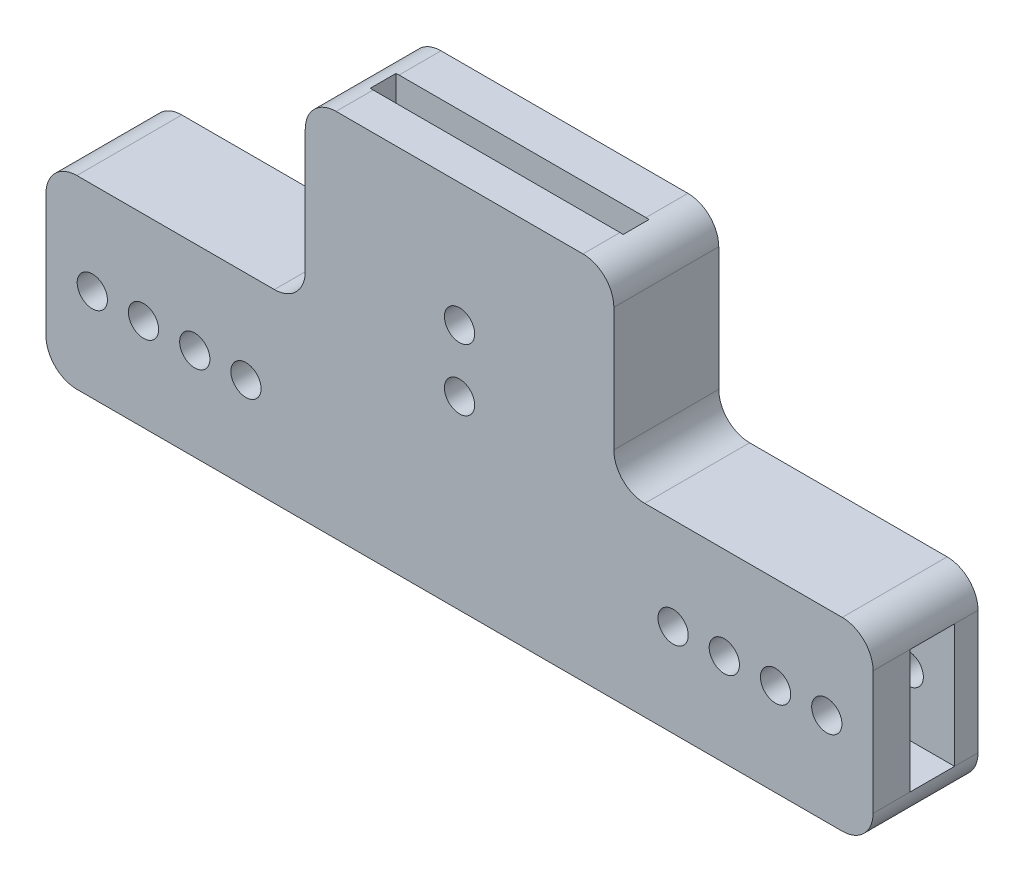
SolidWorks part; units mm, degrees
ref_plane "Front Plane" through (0, 0, 0) normal (0, 0, 1) x (1, 0, 0)
ref_plane "Top Plane" through (0, 0, 0) normal (0, 1, 0) x (1, 0, 0)
ref_plane "Right Plane" through (0, 0, 0) normal (1, 0, 0) x (0, 0, -1)
sketch "Sketch1" plane through (0, 0, 0) normal (0, 0, 1) x (1, 0, 0)
  line L1 (-25, 30) -> (25, 30)
  line L2 (-25, 30) -> (-25, -30)
  line L3 (-25, -30) -> (25, -30)
  line L4 (25, 30) -> (25, -30)
  line L5 (-25, 30) -> (25, -30) construction
  line L6 (-25, -30) -> (25, 30) construction
  point P0 (0, 0)
extrude "Boss-Extrude1" add sketch "Sketch1" along normal blind 12
sketch "Sketch2" plane through (0, 30, 0) normal (0, 1, 0) x (1, 0, 0)
  line L0 (0, 0) -> (0, -12) construction
  line L1 (-20.5, -6.8) -> (20.5, -6.8)
  line L2 (-20.5, -6.8) -> (-20.5, -11)
  line L3 (-20.5, -11) -> (20.5, -11)
  line L4 (20.5, -6.8) -> (20.5, -11)
  line L5 (-20.5, -6.8) -> (20.5, -11) construction
  line L6 (-20.5, -11) -> (20.5, -6.8) construction
  line L7 (25, 0) -> (-25, 0) construction
  line L8 (-25, -6) -> (25, -6) construction
  line L9 (-25, -12) -> (-25, 0) construction
  line L10 (25, -12) -> (25, 0) construction
  line L11 (25, -12) -> (-25, -12) construction
  point P0 (0, -8.9)
  dimension "D1" = 1
  dimension "D2" = 4.2
  dimension "D3" = 41
extrude "Cut-Extrude1" cut sketch "Sketch2" against normal through all
sketch "Sketch3" plane through (-25, 0, 0) normal (-1, 0, 0) x (0, 0, 1)
  line L0 (12, 30) -> (12, -30) construction
  line L1 (0, -30) -> (12, -30)
  line L2 (0, -30) -> (0, 0)
  line L3 (0, 0) -> (12, 0)
  line L4 (12, -30) -> (12, 0)
  line L5 (6, 0) -> (6, -30) construction
  line L6 (0, -15) -> (12, -15) construction
  point P1024 (6, -15)
  dimension "D1" = 30
extrude "Boss-Extrude2" add sketch "Sketch3" along normal blind 42
sketch "Sketch4" plane through (-67, 0, 0) normal (-1, 0, 0) x (0, 0, 1)
  line L0 (12, 0) -> (0, 0) construction
  line L1 (3.8, -5) -> (11, -5)
  line L2 (3.8, -5) -> (3.8, -25)
  line L3 (3.8, -25) -> (11, -25)
  line L4 (11, -5) -> (11, -25)
  line L5 (3.8, -5) -> (11, -25) construction
  line L6 (3.8, -25) -> (11, -5) construction
  line L7 (12, -30) -> (12, 0) construction
  line L9 (0, -30) -> (12, -30) construction
  line L10 (6, 0) -> (6, -30) construction
  point P0 (7.4, -15)
  dimension "D1" = 5
  dimension "D2" = 1
  dimension "D3" = 7.2
  dimension "D4" = 5
extrude "Cut-Extrude2" cut sketch "Sketch4" against normal blind 42.5
sketch "Sketch5" plane through (0, 0, 12) normal (0, 0, 1) x (1, 0, 0)
  line L0 (-67, -5) -> (-67, -25) construction
  circle A0 centre (-59.5, -14.9958) radius 2.45
  circle A1 centre (-51.2, -14.9958) radius 2.45
  circle A2 centre (-42.9, -14.9958) radius 2.45
  circle A3 centre (-34.6, -14.9958) radius 2.45
  dimension "D1" = 4
  dimension "D3" = 4.9
  dimension "D4" = 4.9
  dimension "D2" = 7.5
extrude "Cut-Extrude3" cut sketch "Sketch5" against normal mid plane 35
mirror "Mirror1" about plane through (0, 0, 0) normal (1, 0, 0) of "Cut-Extrude3", "Cut-Extrude2", "Boss-Extrude2"
fillet "Fillet1" radius 5 8 edges at (67, -30, 6) (67, 0, 6) (25, 0, 6) (-67, -30, 6) (-67, 0, 6) (-25, 0, 6) (25, 30, 6) (-25, 30, 6)
sketch "Sketch6" plane through (0, 0, 12) normal (0, 0, 1) x (1, 0, 0)
  circle A0 centre (0, 0) radius 2.45
  circle A1 centre (0, 10) radius 2.45
  dimension "D1" = 10
  dimension "D2" = 4.9
  dimension "D3" = 4.9
extrude "Cut-Extrude4" cut sketch "Sketch6" against normal blind 35
sketch "Sketch7" plane through (0, 0, 12) normal (0, 0, 1) x (1, 0, 0)
  line L0 (-30, 0) -> (-62, 0)
  line L1 (-67, -5) -> (-67, -25)
  line L2 (-62, -30) -> (62, -30)
  line L3 (67, -25) -> (67, -5)
  line L4 (62, 0) -> (30, 0)
  line L5 (25, 5) -> (25, 25)
  line L6 (20, 30) -> (-20, 30)
  circle A0 centre (0, 0) radius 2.45
  circle A1 centre (0, 10) radius 2.45
  circle A2 centre (34.6, -14.9958) radius 2.45
  circle A3 centre (42.9, -14.9958) radius 2.45
  circle A4 centre (51.2, -14.9958) radius 2.45
  circle A5 centre (59.5, -14.9958) radius 2.45
  circle A6 centre (-34.6, -14.9958) radius 2.45
  circle A7 centre (-42.9, -14.9958) radius 2.45
  circle A8 centre (-51.2, -14.9958) radius 2.45
  circle A9 centre (-59.5, -14.9958) radius 2.45
  arc A10 (-20, 30) -> (-24.8892, 26.0468) centre (-20, 25) ccw
  arc A11 (-20, 30) -> (-25, 25) centre (-20, 25) ccw construction
  arc A12 (-62, 0) -> (-67, -5) centre (-62, -5) ccw
  arc A13 (-67, -25) -> (-62, -30) centre (-62, -25) ccw
  arc A14 (62, -30) -> (67, -25) centre (62, -25) ccw
  arc A15 (67, -5) -> (62, 0) centre (62, -5) ccw
  arc A16 (25, 25) -> (20, 30) centre (20, 25) ccw
  arc A17 (25, 5) -> (30, 0) centre (30, 5) ccw
  line M15 (-62, -30) -> (62, -30)
  arc M16 (62, -30) -> (67, -25) centre (62, -25) ccw
  line M17 (67, -25) -> (67, -5)
  arc M18 (67, -5) -> (62, 0) centre (62, -5) ccw
  line M19 (62, 0) -> (30, 0)
  arc M20 (30, 0) -> (25, 5) centre (30, 5) cw
  line M21 (25, 5) -> (25, 25)
  arc M22 (25, 25) -> (20, 30) centre (20, 25) ccw
  line M23 (20, 30) -> (-20, 30)
  arc M24 (-20, 30) -> (-25, 25) centre (-20, 25) ccw
  line M25 (-25, 25) -> (-25, 5)
  arc M26 (-25, 5) -> (-30, 0) centre (-30, 5) cw
  line M27 (-30, 0) -> (-62, 0)
  arc M28 (-62, 0) -> (-67, -5) centre (-62, -5) ccw
  line M29 (-67, -5) -> (-67, -25)
  arc M30 (-67, -25) -> (-62, -30) centre (-62, -25) ccw
  dimension "D1" = 4.9
extrude "Boss-Extrude3" add sketch "Sketch7" along normal blind 5 contours A9 A8 A7 A6 A5 A4 A3 A2 A1 A0 M30 M15 M16 M17 M18 M19 M20 M21 M22 M23 M24 M25 M26 M27 M28 M29 region at (0, -6.7237, 12)
